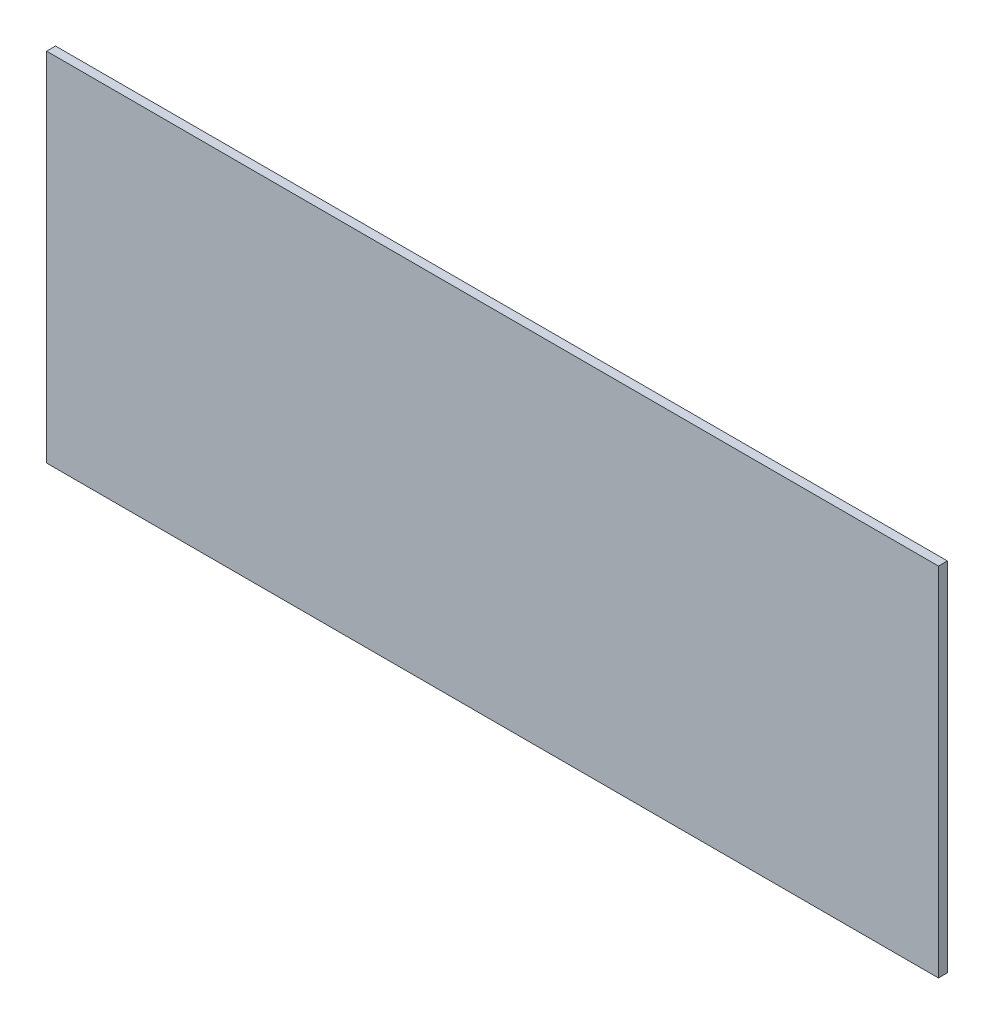
SolidWorks part; units mm, degrees
material "Eiche"
ref_plane "Ebene vorne" through (0, 0, 0) normal (0, 0, 1) x (1, 0, 0)
ref_plane "Ebene oben" through (0, 0, 0) normal (0, 1, 0) x (1, 0, 0)
ref_plane "Ebene rechts" through (0, 0, 0) normal (1, 0, 0) x (0, 0, -1)
sketch "Skizze1" plane through (0, 0, 0) normal (0, 0, 1) x (1, 0, 0)
  line L1 (0, 0) -> (10000, 0)
  line L2 (0, 0) -> (0, 4000)
  line L3 (0, 4000) -> (10000, 4000)
  line L4 (10000, 0) -> (10000, 4000)
  dimension "D1" = 10000
  dimension "D2" = 4000
extrude "Aufsatz-Linear austragen1" add sketch "Skizze1" along normal blind 100
